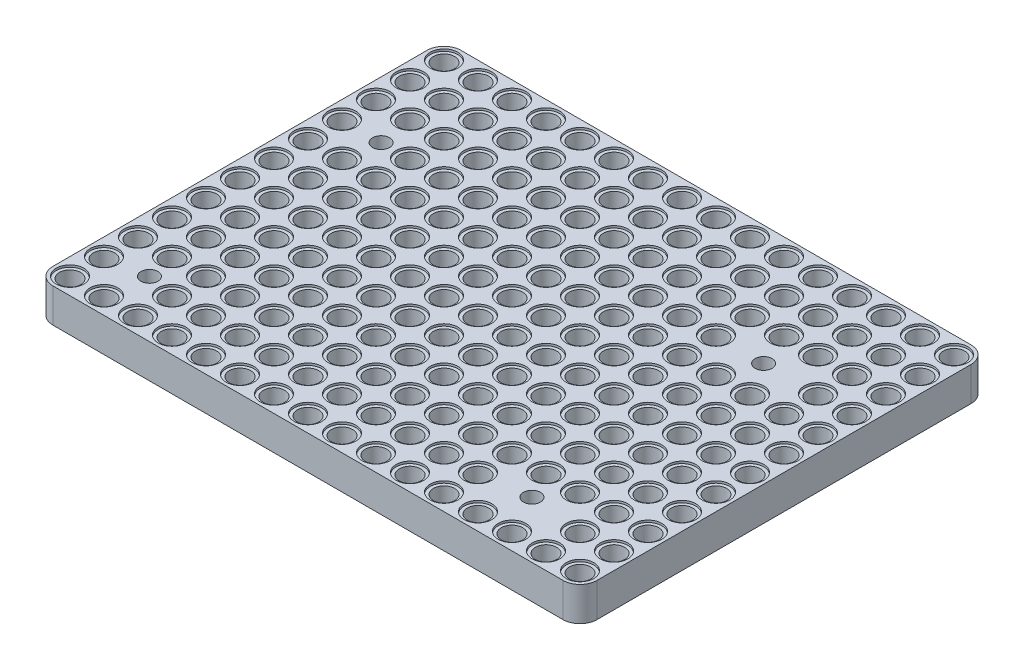
SolidWorks part; units mm, degrees
ref_plane "Спереди" through (0, 0, 0) normal (0, 0, 1) x (1, 0, 0)
ref_plane "Сверху" through (0, 0, 0) normal (0, 1, 0) x (1, 0, 0)
ref_plane "Справа" through (0, 0, 0) normal (1, 0, 0) x (0, 0, -1)
other "Configuration Table"
sketch "Эскиз1" plane through (0, 0, 0) normal (0, 1, 0) x (1, 0, 0)
  line L0 (-207.6024, -2.8) -> (124.1119, -2.8) construction
  line L1 (0, 0) -> (90, 0) construction
  line L2 (0, 0) -> (0, 54.5) construction
  line L3 (0, 54.5) -> (90, 54.5) construction
  line L4 (90, 0) -> (90, 54.5) construction
  line L5 (-2.4, 114.0429) -> (-2.4, -79.8429) construction
  line L6 (-13.4, 115.1755) -> (-13.4, -43.2774) construction
  line L7 (-2.4, -2.8) -> (103.1, -2.8) construction
  line L8 (-2.4, -2.8) -> (-2.4, 72.2) construction
  line L9 (-2.4, 72.2) -> (103.1, 72.2) construction
  line L10 (103.1, -2.8) -> (103.1, 72.2) construction
  line L11 (114.6, 128.3799) -> (114.6, -43.2774) construction
  line L12 (-57.6548, -13.3) -> (114.6196, -13.3) construction
  line L13 (-66.5435, 82.7) -> (173.2488, 82.7) construction
  line L15 (-9.4, -13.3) -> (110.6, -13.3)
  line L16 (-13.4, -9.3) -> (-13.4, 78.7)
  line L17 (-9.4, 82.7) -> (110.6, 82.7)
  line L18 (114.6, -9.3) -> (114.6, 78.7)
  line L19 (-13.4, 82.7) -> (-9.4, 82.7) construction
  line L20 (-13.4, 82.7) -> (-13.4, 78.7) construction
  line L21 (-13.4, 78.7) -> (-9.4, 78.7) construction
  line L22 (-9.4, 82.7) -> (-9.4, 78.7) construction
  circle A0 centre (-9.4, 78.7) radius 2.5
  circle A1 centre (-1.4, 78.7) radius 2.5
  circle A2 centre (6.6, 78.7) radius 2.5
  circle A3 centre (14.6, 78.7) radius 2.5
  circle A4 centre (22.6, 78.7) radius 2.5
  circle A5 centre (30.6, 78.7) radius 2.5
  circle A6 centre (38.6, 78.7) radius 2.5
  circle A7 centre (46.6, 78.7) radius 2.5
  circle A8 centre (54.6, 78.7) radius 2.5
  circle A9 centre (62.6, 78.7) radius 2.5
  circle A10 centre (70.6, 78.7) radius 2.5
  circle A11 centre (78.6, 78.7) radius 2.5
  circle A12 centre (86.6, 78.7) radius 2.5
  circle A13 centre (94.6, 78.7) radius 2.5
  circle A14 centre (102.6, 78.7) radius 2.5
  circle A15 centre (110.6, 78.7) radius 2.5
  circle A16 centre (-1.4, 70.7) radius 2.5
  circle A17 centre (6.6, 70.7) radius 2.5
  circle A18 centre (14.6, 70.7) radius 2.5
  circle A19 centre (22.6, 70.7) radius 2.5
  circle A20 centre (30.6, 70.7) radius 2.5
  circle A21 centre (38.6, 70.7) radius 2.5
  circle A22 centre (46.6, 70.7) radius 2.5
  circle A23 centre (54.6, 70.7) radius 2.5
  circle A24 centre (62.6, 70.7) radius 2.5
  circle A25 centre (70.6, 70.7) radius 2.5
  circle A26 centre (78.6, 70.7) radius 2.5
  circle A27 centre (86.6, 70.7) radius 2.5
  circle A28 centre (94.6, 70.7) radius 2.5
  circle A29 centre (102.6, 70.7) radius 2.5
  circle A30 centre (110.6, 70.7) radius 2.5
  circle A31 centre (-1.4, 62.7) radius 2.5
  circle A32 centre (6.6, 62.7) radius 2.5
  circle A33 centre (14.6, 62.7) radius 2.5
  circle A34 centre (22.6, 62.7) radius 2.5
  circle A35 centre (30.6, 62.7) radius 2.5
  circle A36 centre (38.6, 62.7) radius 2.5
  circle A37 centre (46.6, 62.7) radius 2.5
  circle A38 centre (54.6, 62.7) radius 2.5
  circle A39 centre (62.6, 62.7) radius 2.5
  circle A40 centre (70.6, 62.7) radius 2.5
  circle A41 centre (78.6, 62.7) radius 2.5
  circle A42 centre (86.6, 62.7) radius 2.5
  circle A43 centre (94.6, 62.7) radius 2.5
  circle A44 centre (102.6, 62.7) radius 2.5
  circle A45 centre (110.6, 62.7) radius 2.5
  circle A47 centre (6.6, 54.7) radius 2.5
  circle A48 centre (14.6, 54.7) radius 2.5
  circle A49 centre (22.6, 54.7) radius 2.5
  circle A50 centre (30.6, 54.7) radius 2.5
  circle A51 centre (38.6, 54.7) radius 2.5
  circle A52 centre (46.6, 54.7) radius 2.5
  circle A53 centre (54.6, 54.7) radius 2.5
  circle A54 centre (62.6, 54.7) radius 2.5
  circle A55 centre (70.6, 54.7) radius 2.5
  circle A56 centre (78.6, 54.7) radius 2.5
  circle A59 centre (102.6, 54.7) radius 2.5
  circle A60 centre (110.6, 54.7) radius 2.5
  circle A61 centre (-1.4, 46.7) radius 2.5
  circle A62 centre (6.6, 46.7) radius 2.5
  circle A63 centre (14.6, 46.7) radius 2.5
  circle A64 centre (22.6, 46.7) radius 2.5
  circle A65 centre (30.6, 46.7) radius 2.5
  circle A66 centre (38.6, 46.7) radius 2.5
  circle A67 centre (46.6, 46.7) radius 2.5
  circle A68 centre (54.6, 46.7) radius 2.5
  circle A69 centre (62.6, 46.7) radius 2.5
  circle A70 centre (70.6, 46.7) radius 2.5
  circle A71 centre (78.6, 46.7) radius 2.5
  circle A72 centre (86.6, 46.7) radius 2.5
  circle A73 centre (94.6, 46.7) radius 2.5
  circle A74 centre (102.6, 46.7) radius 2.5
  circle A75 centre (110.6, 46.7) radius 2.5
  circle A76 centre (-1.4, 38.7) radius 2.5
  circle A77 centre (6.6, 38.7) radius 2.5
  circle A78 centre (14.6, 38.7) radius 2.5
  circle A79 centre (22.6, 38.7) radius 2.5
  circle A80 centre (30.6, 38.7) radius 2.5
  circle A81 centre (38.6, 38.7) radius 2.5
  circle A82 centre (46.6, 38.7) radius 2.5
  circle A83 centre (54.6, 38.7) radius 2.5
  circle A84 centre (62.6, 38.7) radius 2.5
  circle A85 centre (70.6, 38.7) radius 2.5
  circle A86 centre (78.6, 38.7) radius 2.5
  circle A87 centre (86.6, 38.7) radius 2.5
  circle A88 centre (94.6, 38.7) radius 2.5
  circle A89 centre (102.6, 38.7) radius 2.5
  circle A90 centre (110.6, 38.7) radius 2.5
  circle A91 centre (-1.4, 30.7) radius 2.5
  circle A92 centre (6.6, 30.7) radius 2.5
  circle A93 centre (14.6, 30.7) radius 2.5
  circle A94 centre (22.6, 30.7) radius 2.5
  circle A95 centre (30.6, 30.7) radius 2.5
  circle A96 centre (38.6, 30.7) radius 2.5
  circle A97 centre (46.6, 30.7) radius 2.5
  circle A98 centre (54.6, 30.7) radius 2.5
  circle A99 centre (62.6, 30.7) radius 2.5
  circle A100 centre (70.6, 30.7) radius 2.5
  circle A101 centre (78.6, 30.7) radius 2.5
  circle A102 centre (86.6, 30.7) radius 2.5
  circle A103 centre (94.6, 30.7) radius 2.5
  circle A104 centre (102.6, 30.7) radius 2.5
  circle A105 centre (110.6, 30.7) radius 2.5
  circle A106 centre (-1.4, 22.7) radius 2.5
  circle A107 centre (6.6, 22.7) radius 2.5
  circle A108 centre (14.6, 22.7) radius 2.5
  circle A109 centre (22.6, 22.7) radius 2.5
  circle A110 centre (30.6, 22.7) radius 2.5
  circle A111 centre (38.6, 22.7) radius 2.5
  circle A112 centre (46.6, 22.7) radius 2.5
  circle A113 centre (54.6, 22.7) radius 2.5
  circle A114 centre (62.6, 22.7) radius 2.5
  circle A115 centre (70.6, 22.7) radius 2.5
  circle A116 centre (78.6, 22.7) radius 2.5
  circle A117 centre (86.6, 22.7) radius 2.5
  circle A118 centre (94.6, 22.7) radius 2.5
  circle A119 centre (102.6, 22.7) radius 2.5
  circle A120 centre (110.6, 22.7) radius 2.5
  circle A121 centre (-1.4, 14.7) radius 2.5
  circle A122 centre (6.6, 14.7) radius 2.5
  circle A123 centre (14.6, 14.7) radius 2.5
  circle A124 centre (22.6, 14.7) radius 2.5
  circle A125 centre (30.6, 14.7) radius 2.5
  circle A126 centre (38.6, 14.7) radius 2.5
  circle A127 centre (46.6, 14.7) radius 2.5
  circle A128 centre (54.6, 14.7) radius 2.5
  circle A129 centre (62.6, 14.7) radius 2.5
  circle A130 centre (70.6, 14.7) radius 2.5
  circle A131 centre (78.6, 14.7) radius 2.5
  circle A132 centre (86.6, 14.7) radius 2.5
  circle A133 centre (94.6, 14.7) radius 2.5
  circle A134 centre (102.6, 14.7) radius 2.5
  circle A135 centre (110.6, 14.7) radius 2.5
  circle A136 centre (-1.4, 6.7) radius 2.5
  circle A137 centre (6.6, 6.7) radius 2.5
  circle A138 centre (14.6, 6.7) radius 2.5
  circle A139 centre (22.6, 6.7) radius 2.5
  circle A140 centre (30.6, 6.7) radius 2.5
  circle A141 centre (38.6, 6.7) radius 2.5
  circle A142 centre (46.6, 6.7) radius 2.5
  circle A143 centre (54.6, 6.7) radius 2.5
  circle A144 centre (62.6, 6.7) radius 2.5
  circle A145 centre (70.6, 6.7) radius 2.5
  circle A146 centre (78.6, 6.7) radius 2.5
  circle A147 centre (86.6, 6.7) radius 2.5
  circle A148 centre (94.6, 6.7) radius 2.5
  circle A149 centre (102.6, 6.7) radius 2.5
  circle A150 centre (110.6, 6.7) radius 2.5
  circle A152 centre (6.6, -1.3) radius 2.5
  circle A153 centre (14.6, -1.3) radius 2.5
  circle A154 centre (22.6, -1.3) radius 2.5
  circle A155 centre (30.6, -1.3) radius 2.5
  circle A156 centre (38.6, -1.3) radius 2.5
  circle A157 centre (46.6, -1.3) radius 2.5
  circle A158 centre (54.6, -1.3) radius 2.5
  circle A159 centre (62.6, -1.3) radius 2.5
  circle A160 centre (70.6, -1.3) radius 2.5
  circle A161 centre (78.6, -1.3) radius 2.5
  circle A164 centre (102.6, -1.3) radius 2.5
  circle A165 centre (110.6, -1.3) radius 2.5
  circle A166 centre (-1.4, -9.3) radius 2.5
  circle A167 centre (6.6, -9.3) radius 2.5
  circle A168 centre (14.6, -9.3) radius 2.5
  circle A169 centre (22.6, -9.3) radius 2.5
  circle A170 centre (30.6, -9.3) radius 2.5
  circle A171 centre (38.6, -9.3) radius 2.5
  circle A172 centre (46.6, -9.3) radius 2.5
  circle A173 centre (54.6, -9.3) radius 2.5
  circle A174 centre (62.6, -9.3) radius 2.5
  circle A175 centre (70.6, -9.3) radius 2.5
  circle A176 centre (78.6, -9.3) radius 2.5
  circle A177 centre (86.6, -9.3) radius 2.5
  circle A178 centre (94.6, -9.3) radius 2.5
  circle A179 centre (102.6, -9.3) radius 2.5
  circle A180 centre (110.6, -9.3) radius 2.5
  circle A181 centre (-9.4, 70.7) radius 2.5
  circle A182 centre (-9.4, 62.7) radius 2.5
  circle A183 centre (-9.4, 54.7) radius 2.5
  circle A184 centre (-9.4, 46.7) radius 2.5
  circle A185 centre (-9.4, 38.7) radius 2.5
  circle A186 centre (-9.4, 30.7) radius 2.5
  circle A187 centre (-9.4, 22.7) radius 2.5
  circle A188 centre (-9.4, 14.7) radius 2.5
  circle A189 centre (-9.4, 6.7) radius 2.5
  circle A190 centre (-9.4, -1.3) radius 2.5
  circle A191 centre (-9.4, -9.3) radius 2.5
  circle A192 centre (-1.4, -1.3) radius 2.5 [skipped]
  circle A193 centre (86.6, -1.3) radius 2.5 [skipped]
  circle A194 centre (86.6, 54.7) radius 2.5 [skipped]
  circle A195 centre (-1.4, 54.7) radius 2.5 [skipped]
  circle A196 centre (0, 54.5) radius 2
  circle A197 centre (90, 54.5) radius 2
  circle A198 centre (90, 0) radius 2
  circle A199 centre (0, 0) radius 2
  circle A200 centre (94.6, 54.7) radius 2.5 [skipped]
  circle A201 centre (94.6, -1.3) radius 2.5 [skipped]
  arc A202 (-13.4, -9.3) -> (-9.4, -13.3) centre (-9.4, -9.3) ccw
  arc A203 (114.6, -9.3) -> (110.6, -13.3) centre (110.6, -9.3) cw
  arc A204 (114.6, 78.7) -> (110.6, 82.7) centre (110.6, 78.7) ccw
  arc A205 (-13.4, 78.7) -> (-9.4, 82.7) centre (-9.4, 78.7) cw
  point P145 (-13.4, -13.3)
  point P354 (114.6, 82.7)
  dimension "D14" = 5
  dimension "D17" = 4
  dimension "D18" = 4
  dimension "D1" = 90
  dimension "D2" = 54.5
  dimension "D3" = 2.4
  dimension "D4" = 2.8
  dimension "D5" = 105.5
  dimension "D6" = 75
  dimension "D7" = 11
  dimension "D8" = 128
  dimension "D9" = 11.5
  dimension "D10" = 10.5
  dimension "D11" = 96
  dimension "D12" = 4
  dimension "D13" = 4
  dimension "D15" = 16
  dimension "D16" = 12
extrude "Бобышка-Вытянуть1" add sketch "Эскиз1" along normal blind 8
sketch "Эскиз2" plane through (0, 8, 0) normal (0, 1, 0) x (1, 0, 0)
  circle A0 centre (-9.4, 78.7) radius 3.25
  circle A1 centre (-1.4, 78.7) radius 3.25
  circle A2 centre (6.6, 78.7) radius 3.25
  circle A3 centre (14.6, 78.7) radius 3.25
  circle A4 centre (22.6, 78.7) radius 3.25
  circle A5 centre (30.6, 78.7) radius 3.25
  circle A6 centre (38.6, 78.7) radius 3.25
  circle A7 centre (46.6, 78.7) radius 3.25
  circle A8 centre (54.6, 78.7) radius 3.25
  circle A9 centre (62.6, 78.7) radius 3.25
  circle A10 centre (70.6, 78.7) radius 3.25
  circle A11 centre (78.6, 78.7) radius 3.25
  circle A12 centre (86.6, 78.7) radius 3.25
  circle A13 centre (94.6, 78.7) radius 3.25
  circle A14 centre (102.6, 78.7) radius 3.25
  circle A15 centre (110.6, 78.7) radius 3.25
  circle A16 centre (-1.4, 70.7) radius 3.25
  circle A17 centre (6.6, 70.7) radius 3.25
  circle A18 centre (14.6, 70.7) radius 3.25
  circle A19 centre (22.6, 70.7) radius 3.25
  circle A20 centre (30.6, 70.7) radius 3.25
  circle A21 centre (38.6, 70.7) radius 3.25
  circle A22 centre (46.6, 70.7) radius 3.25
  circle A23 centre (54.6, 70.7) radius 3.25
  circle A24 centre (62.6, 70.7) radius 3.25
  circle A25 centre (70.6, 70.7) radius 3.25
  circle A26 centre (78.6, 70.7) radius 3.25
  circle A27 centre (86.6, 70.7) radius 3.25
  circle A28 centre (94.6, 70.7) radius 3.25
  circle A29 centre (102.6, 70.7) radius 3.25
  circle A30 centre (110.6, 70.7) radius 3.25
  circle A31 centre (-1.4, 62.7) radius 3.25
  circle A32 centre (6.6, 62.7) radius 3.25
  circle A33 centre (14.6, 62.7) radius 3.25
  circle A34 centre (22.6, 62.7) radius 3.25
  circle A35 centre (30.6, 62.7) radius 3.25
  circle A36 centre (38.6, 62.7) radius 3.25
  circle A37 centre (46.6, 62.7) radius 3.25
  circle A38 centre (54.6, 62.7) radius 3.25
  circle A39 centre (62.6, 62.7) radius 3.25
  circle A40 centre (70.6, 62.7) radius 3.25
  circle A41 centre (78.6, 62.7) radius 3.25
  circle A42 centre (86.6, 62.7) radius 3.25
  circle A43 centre (94.6, 62.7) radius 3.25
  circle A44 centre (102.6, 62.7) radius 3.25
  circle A45 centre (110.6, 62.7) radius 3.25
  circle A47 centre (6.6, 54.7) radius 3.25
  circle A48 centre (14.6, 54.7) radius 3.25
  circle A49 centre (22.6, 54.7) radius 3.25
  circle A50 centre (30.6, 54.7) radius 3.25
  circle A51 centre (38.6, 54.7) radius 3.25
  circle A52 centre (46.6, 54.7) radius 3.25
  circle A53 centre (54.6, 54.7) radius 3.25
  circle A54 centre (62.6, 54.7) radius 3.25
  circle A55 centre (70.6, 54.7) radius 3.25
  circle A56 centre (78.6, 54.7) radius 3.25
  circle A59 centre (102.6, 54.7) radius 3.25
  circle A60 centre (110.6, 54.7) radius 3.25
  circle A61 centre (-1.4, 46.7) radius 3.25
  circle A62 centre (6.6, 46.7) radius 3.25
  circle A63 centre (14.6, 46.7) radius 3.25
  circle A64 centre (22.6, 46.7) radius 3.25
  circle A65 centre (30.6, 46.7) radius 3.25
  circle A66 centre (38.6, 46.7) radius 3.25
  circle A67 centre (46.6, 46.7) radius 3.25
  circle A68 centre (54.6, 46.7) radius 3.25
  circle A69 centre (62.6, 46.7) radius 3.25
  circle A70 centre (70.6, 46.7) radius 3.25
  circle A71 centre (78.6, 46.7) radius 3.25
  circle A72 centre (86.6, 46.7) radius 3.25
  circle A73 centre (94.6, 46.7) radius 3.25
  circle A74 centre (102.6, 46.7) radius 3.25
  circle A75 centre (110.6, 46.7) radius 3.25
  circle A76 centre (-1.4, 38.7) radius 3.25
  circle A77 centre (6.6, 38.7) radius 3.25
  circle A78 centre (14.6, 38.7) radius 3.25
  circle A79 centre (22.6, 38.7) radius 3.25
  circle A80 centre (30.6, 38.7) radius 3.25
  circle A81 centre (38.6, 38.7) radius 3.25
  circle A82 centre (46.6, 38.7) radius 3.25
  circle A83 centre (54.6, 38.7) radius 3.25
  circle A84 centre (62.6, 38.7) radius 3.25
  circle A85 centre (70.6, 38.7) radius 3.25
  circle A86 centre (78.6, 38.7) radius 3.25
  circle A87 centre (86.6, 38.7) radius 3.25
  circle A88 centre (94.6, 38.7) radius 3.25
  circle A89 centre (102.6, 38.7) radius 3.25
  circle A90 centre (110.6, 38.7) radius 3.25
  circle A91 centre (-1.4, 30.7) radius 3.25
  circle A92 centre (6.6, 30.7) radius 3.25
  circle A93 centre (14.6, 30.7) radius 3.25
  circle A94 centre (22.6, 30.7) radius 3.25
  circle A95 centre (30.6, 30.7) radius 3.25
  circle A96 centre (38.6, 30.7) radius 3.25
  circle A97 centre (46.6, 30.7) radius 3.25
  circle A98 centre (54.6, 30.7) radius 3.25
  circle A99 centre (62.6, 30.7) radius 3.25
  circle A100 centre (70.6, 30.7) radius 3.25
  circle A101 centre (78.6, 30.7) radius 3.25
  circle A102 centre (86.6, 30.7) radius 3.25
  circle A103 centre (94.6, 30.7) radius 3.25
  circle A104 centre (102.6, 30.7) radius 3.25
  circle A105 centre (110.6, 30.7) radius 3.25
  circle A106 centre (-1.4, 22.7) radius 3.25
  circle A107 centre (6.6, 22.7) radius 3.25
  circle A108 centre (14.6, 22.7) radius 3.25
  circle A109 centre (22.6, 22.7) radius 3.25
  circle A110 centre (30.6, 22.7) radius 3.25
  circle A111 centre (38.6, 22.7) radius 3.25
  circle A112 centre (46.6, 22.7) radius 3.25
  circle A113 centre (54.6, 22.7) radius 3.25
  circle A114 centre (62.6, 22.7) radius 3.25
  circle A115 centre (70.6, 22.7) radius 3.25
  circle A116 centre (78.6, 22.7) radius 3.25
  circle A117 centre (86.6, 22.7) radius 3.25
  circle A118 centre (94.6, 22.7) radius 3.25
  circle A119 centre (102.6, 22.7) radius 3.25
  circle A120 centre (110.6, 22.7) radius 3.25
  circle A121 centre (-1.4, 14.7) radius 3.25
  circle A122 centre (6.6, 14.7) radius 3.25
  circle A123 centre (14.6, 14.7) radius 3.25
  circle A124 centre (22.6, 14.7) radius 3.25
  circle A125 centre (30.6, 14.7) radius 3.25
  circle A126 centre (38.6, 14.7) radius 3.25
  circle A127 centre (46.6, 14.7) radius 3.25
  circle A128 centre (54.6, 14.7) radius 3.25
  circle A129 centre (62.6, 14.7) radius 3.25
  circle A130 centre (70.6, 14.7) radius 3.25
  circle A131 centre (78.6, 14.7) radius 3.25
  circle A132 centre (86.6, 14.7) radius 3.25
  circle A133 centre (94.6, 14.7) radius 3.25
  circle A134 centre (102.6, 14.7) radius 3.25
  circle A135 centre (110.6, 14.7) radius 3.25
  circle A136 centre (-1.4, 6.7) radius 3.25
  circle A137 centre (6.6, 6.7) radius 3.25
  circle A138 centre (14.6, 6.7) radius 3.25
  circle A139 centre (22.6, 6.7) radius 3.25
  circle A140 centre (30.6, 6.7) radius 3.25
  circle A141 centre (38.6, 6.7) radius 3.25
  circle A142 centre (46.6, 6.7) radius 3.25
  circle A143 centre (54.6, 6.7) radius 3.25
  circle A144 centre (62.6, 6.7) radius 3.25
  circle A145 centre (70.6, 6.7) radius 3.25
  circle A146 centre (78.6, 6.7) radius 3.25
  circle A147 centre (86.6, 6.7) radius 3.25
  circle A148 centre (94.6, 6.7) radius 3.25
  circle A149 centre (102.6, 6.7) radius 3.25
  circle A150 centre (110.6, 6.7) radius 3.25
  circle A152 centre (6.6, -1.3) radius 3.25
  circle A153 centre (14.6, -1.3) radius 3.25
  circle A154 centre (22.6, -1.3) radius 3.25
  circle A155 centre (30.6, -1.3) radius 3.25
  circle A156 centre (38.6, -1.3) radius 3.25
  circle A157 centre (46.6, -1.3) radius 3.25
  circle A158 centre (54.6, -1.3) radius 3.25
  circle A159 centre (62.6, -1.3) radius 3.25
  circle A160 centre (70.6, -1.3) radius 3.25
  circle A161 centre (78.6, -1.3) radius 3.25
  circle A164 centre (102.6, -1.3) radius 3.25
  circle A165 centre (110.6, -1.3) radius 3.25
  circle A166 centre (-1.4, -9.3) radius 3.25
  circle A167 centre (6.6, -9.3) radius 3.25
  circle A168 centre (14.6, -9.3) radius 3.25
  circle A169 centre (22.6, -9.3) radius 3.25
  circle A170 centre (30.6, -9.3) radius 3.25
  circle A171 centre (38.6, -9.3) radius 3.25
  circle A172 centre (46.6, -9.3) radius 3.25
  circle A173 centre (54.6, -9.3) radius 3.25
  circle A174 centre (62.6, -9.3) radius 3.25
  circle A175 centre (70.6, -9.3) radius 3.25
  circle A176 centre (78.6, -9.3) radius 3.25
  circle A177 centre (86.6, -9.3) radius 3.25
  circle A178 centre (94.6, -9.3) radius 3.25
  circle A179 centre (102.6, -9.3) radius 3.25
  circle A180 centre (110.6, -9.3) radius 3.25
  circle A181 centre (-9.4, 70.7) radius 3.25
  circle A182 centre (-9.4, 62.7) radius 3.25
  circle A183 centre (-9.4, 54.7) radius 3.25
  circle A184 centre (-9.4, 46.7) radius 3.25
  circle A185 centre (-9.4, 38.7) radius 3.25
  circle A186 centre (-9.4, 30.7) radius 3.25
  circle A187 centre (-9.4, 22.7) radius 3.25
  circle A188 centre (-9.4, 14.7) radius 3.25
  circle A189 centre (-9.4, 6.7) radius 3.25
  circle A190 centre (-9.4, -1.3) radius 3.25
  circle A191 centre (-9.4, -9.3) radius 3.25
  circle A192 centre (-1.4, 54.7) radius 3.25 [skipped]
  circle A193 centre (86.6, 54.7) radius 3.25 [skipped]
  circle A194 centre (94.6, 54.7) radius 3.25 [skipped]
  circle A195 centre (94.6, -1.3) radius 3.25 [skipped]
  circle A196 centre (86.6, -1.3) radius 3.25 [skipped]
  circle A197 centre (-1.4, -1.3) radius 3.25 [skipped]
  dimension "D1" = 6.5
  dimension "D2" = 16
  dimension "D3" = 12
extrude "Вырез-Вытянуть1" cut sketch "Эскиз2" against normal blind 0.5
sketch "Эскиз3" plane through (0, 0, 0) normal (0, -1, 0) x (1, 0, 0)
  circle A0 centre (-9.4, -78.7) radius 3.25
  circle A1 centre (-1.4, -78.7) radius 3.25
  circle A2 centre (6.6, -78.7) radius 3.25
  circle A3 centre (14.6, -78.7) radius 3.25
  circle A4 centre (22.6, -78.7) radius 3.25
  circle A5 centre (30.6, -78.7) radius 3.25
  circle A6 centre (38.6, -78.7) radius 3.25
  circle A7 centre (46.6, -78.7) radius 3.25
  circle A8 centre (54.6, -78.7) radius 3.25
  circle A9 centre (62.6, -78.7) radius 3.25
  circle A10 centre (70.6, -78.7) radius 3.25
  circle A11 centre (78.6, -78.7) radius 3.25
  circle A12 centre (86.6, -78.7) radius 3.25
  circle A13 centre (94.6, -78.7) radius 3.25
  circle A14 centre (102.6, -78.7) radius 3.25
  circle A15 centre (110.6, -78.7) radius 3.25
  circle A16 centre (-1.4, -70.7) radius 3.25
  circle A17 centre (6.6, -70.7) radius 3.25
  circle A18 centre (14.6, -70.7) radius 3.25
  circle A19 centre (22.6, -70.7) radius 3.25
  circle A20 centre (30.6, -70.7) radius 3.25
  circle A21 centre (38.6, -70.7) radius 3.25
  circle A22 centre (46.6, -70.7) radius 3.25
  circle A23 centre (54.6, -70.7) radius 3.25
  circle A24 centre (62.6, -70.7) radius 3.25
  circle A25 centre (70.6, -70.7) radius 3.25
  circle A26 centre (78.6, -70.7) radius 3.25
  circle A27 centre (86.6, -70.7) radius 3.25
  circle A28 centre (94.6, -70.7) radius 3.25
  circle A29 centre (102.6, -70.7) radius 3.25
  circle A30 centre (110.6, -70.7) radius 3.25
  circle A31 centre (-1.4, -62.7) radius 3.25
  circle A32 centre (6.6, -62.7) radius 3.25
  circle A33 centre (14.6, -62.7) radius 3.25
  circle A34 centre (22.6, -62.7) radius 3.25
  circle A35 centre (30.6, -62.7) radius 3.25
  circle A36 centre (38.6, -62.7) radius 3.25
  circle A37 centre (46.6, -62.7) radius 3.25
  circle A38 centre (54.6, -62.7) radius 3.25
  circle A39 centre (62.6, -62.7) radius 3.25
  circle A40 centre (70.6, -62.7) radius 3.25
  circle A41 centre (78.6, -62.7) radius 3.25
  circle A42 centre (86.6, -62.7) radius 3.25
  circle A43 centre (94.6, -62.7) radius 3.25
  circle A44 centre (102.6, -62.7) radius 3.25
  circle A45 centre (110.6, -62.7) radius 3.25
  circle A47 centre (6.6, -54.7) radius 3.25
  circle A48 centre (14.6, -54.7) radius 3.25
  circle A49 centre (22.6, -54.7) radius 3.25
  circle A50 centre (30.6, -54.7) radius 3.25
  circle A51 centre (38.6, -54.7) radius 3.25
  circle A52 centre (46.6, -54.7) radius 3.25
  circle A53 centre (54.6, -54.7) radius 3.25
  circle A54 centre (62.6, -54.7) radius 3.25
  circle A55 centre (70.6, -54.7) radius 3.25
  circle A56 centre (78.6, -54.7) radius 3.25
  circle A59 centre (102.6, -54.7) radius 3.25
  circle A60 centre (110.6, -54.7) radius 3.25
  circle A61 centre (-1.4, -46.7) radius 3.25
  circle A62 centre (6.6, -46.7) radius 3.25
  circle A63 centre (14.6, -46.7) radius 3.25
  circle A64 centre (22.6, -46.7) radius 3.25
  circle A65 centre (30.6, -46.7) radius 3.25
  circle A66 centre (38.6, -46.7) radius 3.25
  circle A67 centre (46.6, -46.7) radius 3.25
  circle A68 centre (54.6, -46.7) radius 3.25
  circle A69 centre (62.6, -46.7) radius 3.25
  circle A70 centre (70.6, -46.7) radius 3.25
  circle A71 centre (78.6, -46.7) radius 3.25
  circle A72 centre (86.6, -46.7) radius 3.25
  circle A73 centre (94.6, -46.7) radius 3.25
  circle A74 centre (102.6, -46.7) radius 3.25
  circle A75 centre (110.6, -46.7) radius 3.25
  circle A76 centre (-1.4, -38.7) radius 3.25
  circle A77 centre (6.6, -38.7) radius 3.25
  circle A78 centre (14.6, -38.7) radius 3.25
  circle A79 centre (22.6, -38.7) radius 3.25
  circle A80 centre (30.6, -38.7) radius 3.25
  circle A81 centre (38.6, -38.7) radius 3.25
  circle A82 centre (46.6, -38.7) radius 3.25
  circle A83 centre (54.6, -38.7) radius 3.25
  circle A84 centre (62.6, -38.7) radius 3.25
  circle A85 centre (70.6, -38.7) radius 3.25
  circle A86 centre (78.6, -38.7) radius 3.25
  circle A87 centre (86.6, -38.7) radius 3.25
  circle A88 centre (94.6, -38.7) radius 3.25
  circle A89 centre (102.6, -38.7) radius 3.25
  circle A90 centre (110.6, -38.7) radius 3.25
  circle A91 centre (-1.4, -30.7) radius 3.25
  circle A92 centre (6.6, -30.7) radius 3.25
  circle A93 centre (14.6, -30.7) radius 3.25
  circle A94 centre (22.6, -30.7) radius 3.25
  circle A95 centre (30.6, -30.7) radius 3.25
  circle A96 centre (38.6, -30.7) radius 3.25
  circle A97 centre (46.6, -30.7) radius 3.25
  circle A98 centre (54.6, -30.7) radius 3.25
  circle A99 centre (62.6, -30.7) radius 3.25
  circle A100 centre (70.6, -30.7) radius 3.25
  circle A101 centre (78.6, -30.7) radius 3.25
  circle A102 centre (86.6, -30.7) radius 3.25
  circle A103 centre (94.6, -30.7) radius 3.25
  circle A104 centre (102.6, -30.7) radius 3.25
  circle A105 centre (110.6, -30.7) radius 3.25
  circle A106 centre (-1.4, -22.7) radius 3.25
  circle A107 centre (6.6, -22.7) radius 3.25
  circle A108 centre (14.6, -22.7) radius 3.25
  circle A109 centre (22.6, -22.7) radius 3.25
  circle A110 centre (30.6, -22.7) radius 3.25
  circle A111 centre (38.6, -22.7) radius 3.25
  circle A112 centre (46.6, -22.7) radius 3.25
  circle A113 centre (54.6, -22.7) radius 3.25
  circle A114 centre (62.6, -22.7) radius 3.25
  circle A115 centre (70.6, -22.7) radius 3.25
  circle A116 centre (78.6, -22.7) radius 3.25
  circle A117 centre (86.6, -22.7) radius 3.25
  circle A118 centre (94.6, -22.7) radius 3.25
  circle A119 centre (102.6, -22.7) radius 3.25
  circle A120 centre (110.6, -22.7) radius 3.25
  circle A121 centre (-1.4, -14.7) radius 3.25
  circle A122 centre (6.6, -14.7) radius 3.25
  circle A123 centre (14.6, -14.7) radius 3.25
  circle A124 centre (22.6, -14.7) radius 3.25
  circle A125 centre (30.6, -14.7) radius 3.25
  circle A126 centre (38.6, -14.7) radius 3.25
  circle A127 centre (46.6, -14.7) radius 3.25
  circle A128 centre (54.6, -14.7) radius 3.25
  circle A129 centre (62.6, -14.7) radius 3.25
  circle A130 centre (70.6, -14.7) radius 3.25
  circle A131 centre (78.6, -14.7) radius 3.25
  circle A132 centre (86.6, -14.7) radius 3.25
  circle A133 centre (94.6, -14.7) radius 3.25
  circle A134 centre (102.6, -14.7) radius 3.25
  circle A135 centre (110.6, -14.7) radius 3.25
  circle A136 centre (-1.4, -6.7) radius 3.25
  circle A137 centre (6.6, -6.7) radius 3.25
  circle A138 centre (14.6, -6.7) radius 3.25
  circle A139 centre (22.6, -6.7) radius 3.25
  circle A140 centre (30.6, -6.7) radius 3.25
  circle A141 centre (38.6, -6.7) radius 3.25
  circle A142 centre (46.6, -6.7) radius 3.25
  circle A143 centre (54.6, -6.7) radius 3.25
  circle A144 centre (62.6, -6.7) radius 3.25
  circle A145 centre (70.6, -6.7) radius 3.25
  circle A146 centre (78.6, -6.7) radius 3.25
  circle A147 centre (86.6, -6.7) radius 3.25
  circle A148 centre (94.6, -6.7) radius 3.25
  circle A149 centre (102.6, -6.7) radius 3.25
  circle A150 centre (110.6, -6.7) radius 3.25
  circle A152 centre (6.6, 1.3) radius 3.25
  circle A153 centre (14.6, 1.3) radius 3.25
  circle A154 centre (22.6, 1.3) radius 3.25
  circle A155 centre (30.6, 1.3) radius 3.25
  circle A156 centre (38.6, 1.3) radius 3.25
  circle A157 centre (46.6, 1.3) radius 3.25
  circle A158 centre (54.6, 1.3) radius 3.25
  circle A159 centre (62.6, 1.3) radius 3.25
  circle A160 centre (70.6, 1.3) radius 3.25
  circle A161 centre (78.6, 1.3) radius 3.25
  circle A164 centre (102.6, 1.3) radius 3.25
  circle A165 centre (110.6, 1.3) radius 3.25
  circle A166 centre (-1.4, 9.3) radius 3.25
  circle A167 centre (6.6, 9.3) radius 3.25
  circle A168 centre (14.6, 9.3) radius 3.25
  circle A169 centre (22.6, 9.3) radius 3.25
  circle A170 centre (30.6, 9.3) radius 3.25
  circle A171 centre (38.6, 9.3) radius 3.25
  circle A172 centre (46.6, 9.3) radius 3.25
  circle A173 centre (54.6, 9.3) radius 3.25
  circle A174 centre (62.6, 9.3) radius 3.25
  circle A175 centre (70.6, 9.3) radius 3.25
  circle A176 centre (78.6, 9.3) radius 3.25
  circle A177 centre (86.6, 9.3) radius 3.25
  circle A178 centre (94.6, 9.3) radius 3.25
  circle A179 centre (102.6, 9.3) radius 3.25
  circle A180 centre (110.6, 9.3) radius 3.25
  circle A181 centre (-9.4, -70.7) radius 3.25
  circle A182 centre (-9.4, -62.7) radius 3.25
  circle A183 centre (-9.4, -54.7) radius 3.25
  circle A184 centre (-9.4, -46.7) radius 3.25
  circle A185 centre (-9.4, -38.7) radius 3.25
  circle A186 centre (-9.4, -30.7) radius 3.25
  circle A187 centre (-9.4, -22.7) radius 3.25
  circle A188 centre (-9.4, -14.7) radius 3.25
  circle A189 centre (-9.4, -6.7) radius 3.25
  circle A190 centre (-9.4, 1.3) radius 3.25
  circle A191 centre (-9.4, 9.3) radius 3.25
  circle A192 centre (-1.4, 1.3) radius 3.25 [skipped]
  circle A193 centre (-1.4, -54.7) radius 3.25 [skipped]
  circle A194 centre (86.6, -54.7) radius 3.25 [skipped]
  circle A195 centre (94.6, -54.7) radius 3.25 [skipped]
  circle A196 centre (86.6, 1.3) radius 3.25 [skipped]
  circle A197 centre (94.6, 1.3) radius 3.25 [skipped]
  dimension "D1" = 6.5
  dimension "D2" = 16
  dimension "D3" = 12
extrude "Вырез-Вытянуть2" cut sketch "Эскиз3" against normal blind 0.5
